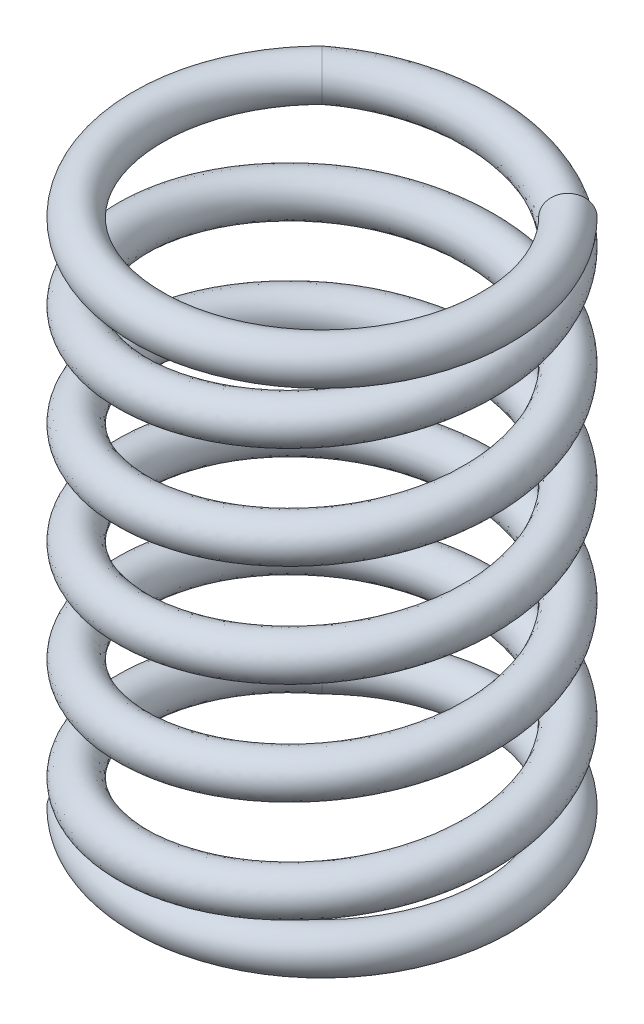
SolidWorks part; units mm, degrees
note: '?' marks a value the reader was unsure of.
ref_plane "Alzado" through (0, 0, 0) normal (0, 0, 1) x (1, 0, 0)
ref_plane "Planta" through (0, 0, 0) normal (0, 1, 0) x (1, 0, 0)
ref_plane "Vista lateral" through (0, 0, 0) normal (1, 0, 0) x (0, 0, -1)
sketch "Croquis1" plane through (0, 0, 0) normal (0, 1, 0) x (1, 0, 0)
  circle A0 centre (0, 0) radius 3.405
  dimension "D1" = 6.81
curve "Hélice/Espiral1" pitch 2 height 10 radius 3.405 centre (0, 0, 0) axis (0, 1, 0) start towards (0, 0, 1)
sketch "Croquis2" plane through (0, 0, 0) normal (0, 0, 1) x (1, 0, 0)
  line L0 (0, 0) -> (0, 9.3335) construction
ref_plane "Plano1" through (0, 0, 0) normal (-0.7071, 0, 0.7071) x (0.7071, 0, 0.7071)
sketch "Croquis3" plane through (0, 0, 0) normal (-0.7071, 0, 0.7071) x (0.7071, 0, 0.7071)
  circle A0 centre (-3.405, 10) radius 0.405
  dimension "D1" = 0.81
sweep "Barrer1" add profiles "Croquis3" path "Hélice/Espiral1"
sketch "Croquis4" plane through (0, 0, 0) normal (-0.7071, 0, 0.7071) x (0.7071, 0, 0.7071)
  circle A0 centre (-3.405, 10) radius 0.405 construction
  circle A1 centre (-3.405, 10) radius 0.405
revolve "Revolución1" add sketch "Croquis4" angle 270 about L0
sketch "Croquis6" plane through (0, 0, 0) normal (0.7071, 0, -0.7071) x (-0.7071, 0, -0.7071)
  circle A0 centre (3.405, 0) radius 0.405 construction
  circle A1 centre (3.405, 0) radius 0.405
revolve "Revolución2" add sketch "Croquis6" angle 270 about L0 reverse direction yes
ref_axis "Eje1" through (0, 11.391, 0) along (0, -1, 0)?
